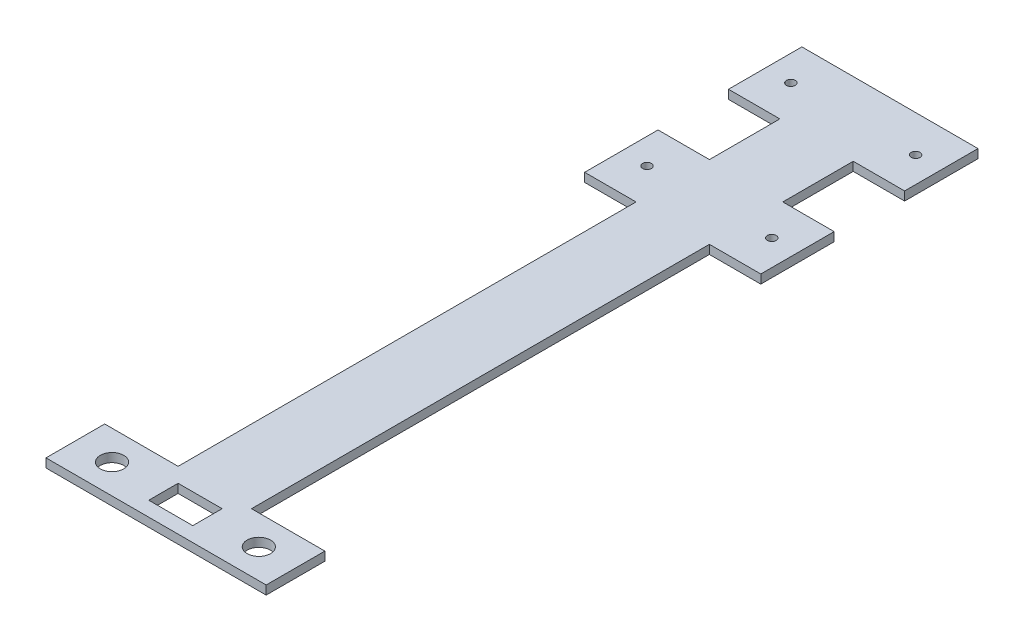
SolidWorks part; units mm, degrees
ref_plane "Front Plane" through (0, 0, 0) normal (0, 0, 1) x (1, 0, 0)
ref_plane "Top Plane" through (0, 0, 0) normal (0, 1, 0) x (1, 0, 0)
ref_plane "Right Plane" through (0, 0, 0) normal (1, 0, 0) x (0, 0, -1)
sketch "Sketch1" plane through (0, 0, 0) normal (0, 1, 0) x (1, 0, 0)
  line L0 (12.5, 76) -> (30, 76)
  line L1 (-12.5, -125) -> (12.5, -125)
  line L2 (-12.5, -125) -> (-12.5, 125)
  line L3 (-12.5, 125) -> (12.5, 125)
  line L4 (12.5, -125) -> (12.5, 125)
  line L5 (-12.5, -125) -> (12.5, 125) construction
  line L6 (-12.5, 125) -> (12.5, -125) construction
  line L7 (30, 76) -> (30, 51)
  line L8 (30, 51) -> (12.5, 51)
  line L9 (0, -125) -> (0, 125) construction
  line L10 (-30, 51) -> (-12.5, 51)
  line L11 (-30, 76) -> (-30, 51)
  line L12 (-12.5, 76) -> (-30, 76)
  line L13 (12.5, 100) -> (30, 100)
  line L14 (30, 100) -> (30, 125)
  line L15 (30, 125) -> (12.5, 125)
  line L16 (-30, 125) -> (-12.5, 125)
  line L17 (-30, 100) -> (-30, 125)
  line L18 (-12.5, 100) -> (-30, 100)
  line L19 (-12.5, -125) -> (-37.5, -125)
  line L20 (-37.5, -125) -> (-37.5, -105)
  line L21 (-37.5, -105) -> (-12.5, -105)
  line L22 (12.5, -125) -> (37.5, -125)
  line L23 (37.5, -125) -> (37.5, -105)
  line L24 (37.5, -105) -> (12.5, -105)
  point P0 (0, 0)
  dimension "D1" = 250
  dimension "D2" = 25
  dimension "D3" = 60
  dimension "D4" = 25
  dimension "D5" = 0
  dimension "D6" = 24
  dimension "D7" = 25
  dimension "D8" = 20
  dimension "D9" = 25
extrude "Boss-Extrude1" add sketch "Sketch1" along normal blind 3 contours L8 L7 L0 L4 | L1 L4 L3 L2 | L2 L12 L11 L10 | L14 L15 L4 L13 | L18 L2 L16 L17 | L21 L20 L19 L2 | L23 L24 L4 L22 region at (21.25, 0, -63.5) region at (0, 0, 0) region at (21.25, 0, -112.5) region at (25, 0, 115) region at (-21.25, 0, -112.5) region at (-25, 0, 115) region at (-21.25, 0, -63.5)
sketch "Sketch2" plane through (0, 3, 0) normal (0, 1, 0) x (1, 0, 0)
  line L0 (30, 112.5) -> (-30, 112.5) construction
  line L3 (30, 100) -> (30, 125) construction
  line L6 (0, 0) -> (0, -125) construction
  line L7 (-30, 100) -> (-30, 125) construction
  line L8 (0, 125) -> (0, -125) construction
  line L9 (-37.5, -125) -> (37.5, -125) construction
  line L10 (-30, 125) -> (30, 125) construction
  line L11 (-30, 63.5) -> (30, 63.5) construction
  line L12 (-30, 76) -> (-30, 51) construction
  line L15 (30, 76) -> (30, 51) construction
  circle A0 centre (-21.25, 112.5) radius 1.5
  circle A1 centre (21.25, 112.5) radius 1.5
  circle A2 centre (-21.25, 63.5) radius 1.5
  circle A4 centre (21.25, 63.5) radius 1.5
  dimension "D1" = 3
  dimension "D2" = 42.5
  dimension "D3" = 42.5
  dimension "D4" = 3
extrude "Cut-Extrude1" cut sketch "Sketch2" against normal through all both and the other way through all
sketch "Sketch3" plane through (0, 3, 0) normal (0, 1, 0) x (1, 0, 0)
  line L0 (-37.5, -115) -> (37.5, -115) construction
  line L1 (-37.5, -125) -> (-37.5, -105) construction
  line L2 (37.5, -125) -> (37.5, -105) construction
  line L3 (0, -125) -> (0, 0) construction
  line L4 (-37.5, -125) -> (37.5, -125) construction
  line L6 (-7.5, -120) -> (7.5, -120)
  line L7 (-7.5, -120) -> (-7.5, -110)
  line L8 (-7.5, -110) -> (7.5, -110)
  line L9 (7.5, -120) -> (7.5, -110)
  line L10 (-7.5, -120) -> (7.5, -110) construction
  line L11 (-7.5, -110) -> (7.5, -120) construction
  circle A0 centre (-25, -115) radius 4
  circle A1 centre (25, -115) radius 4
  point P11 (0, -115)
  dimension "D3" = 8
  dimension "D4" = 50
  dimension "D1" = 15
  dimension "D2" = 10
extrude "Cut-Extrude2" cut sketch "Sketch3" against normal through all both and the other way through all
